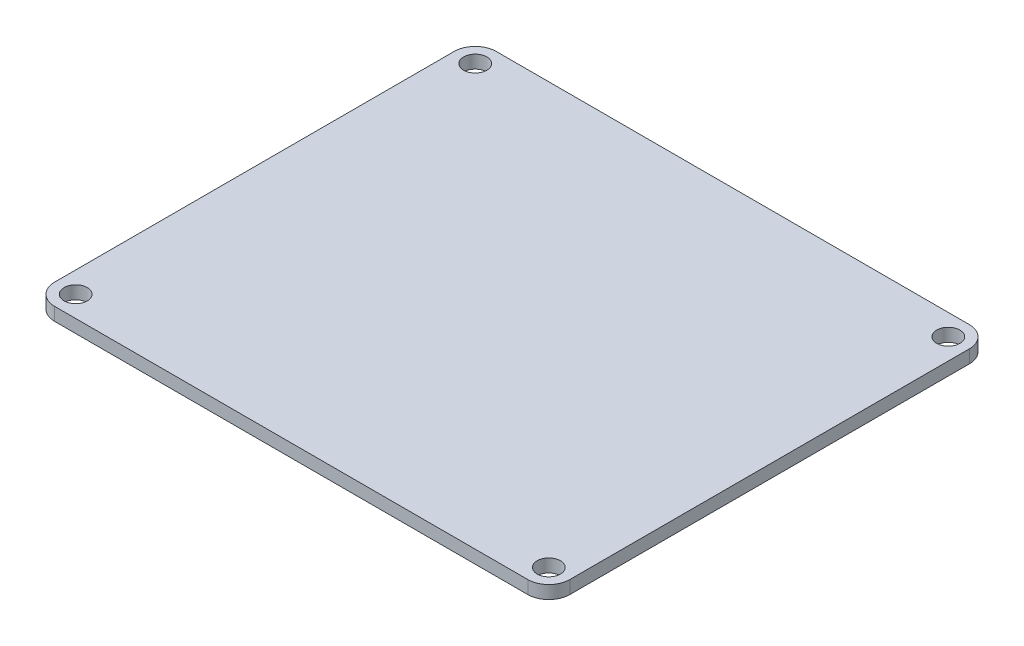
SolidWorks part; units mm, degrees
ref_plane "Front Plane" through (0, 0, 0) normal (0, 0, 1) x (1, 0, 0)
ref_plane "Top Plane" through (0, 0, 0) normal (0, 1, 0) x (1, 0, 0)
ref_plane "Right Plane" through (0, 0, 0) normal (1, 0, 0) x (0, 0, -1)
sketch "Sketch1" plane through (0, 0, 0) normal (0, 1, 0) x (1, 0, 0)
  line L1 (-28.575, 26.67) -> (28.575, 26.67)
  line L2 (-31.115, 24.13) -> (-31.115, -24.13)
  line L3 (-28.575, -26.67) -> (28.575, -26.67)
  line L4 (31.115, 24.13) -> (31.115, -24.13)
  line L5 (-31.115, 26.67) -> (31.115, -26.67) construction
  line L6 (-31.115, -26.67) -> (31.115, 26.67) construction
  circle A0 centre (-28.575, 24.13) radius 1.4
  circle A1 centre (28.575, 24.13) radius 1.4
  circle A2 centre (-28.575, -24.13) radius 1.4
  circle A3 centre (28.575, -24.13) radius 1.4
  arc A4 (28.575, 26.67) -> (31.115, 24.13) centre (28.575, 24.13) cw
  arc A5 (28.575, -26.67) -> (31.115, -24.13) centre (28.575, -24.13) ccw
  arc A6 (-31.115, -24.13) -> (-28.575, -26.67) centre (-28.575, -24.13) ccw
  arc A7 (-28.575, 26.67) -> (-31.115, 24.13) centre (-28.575, 24.13) ccw
  point P0 (0, 0)
  dimension "D3" = 2.8
  dimension "D4" = 2.8
  dimension "D5" = 2.8
  dimension "D6" = 2.8
  dimension "D15" = 2.54
  dimension "D1" = 62.23
  dimension "D2" = 53.34
  dimension "D7" = 2.54
  dimension "D8" = 2.54
  dimension "D9" = 2.54
  dimension "D10" = 2.54
  dimension "D11" = 2.54
  dimension "D12" = 2.54
  dimension "D13" = 2.54
  dimension "D14" = 2.54
extrude "Boss-Extrude1" add sketch "Sketch1" along normal blind 1.5748
